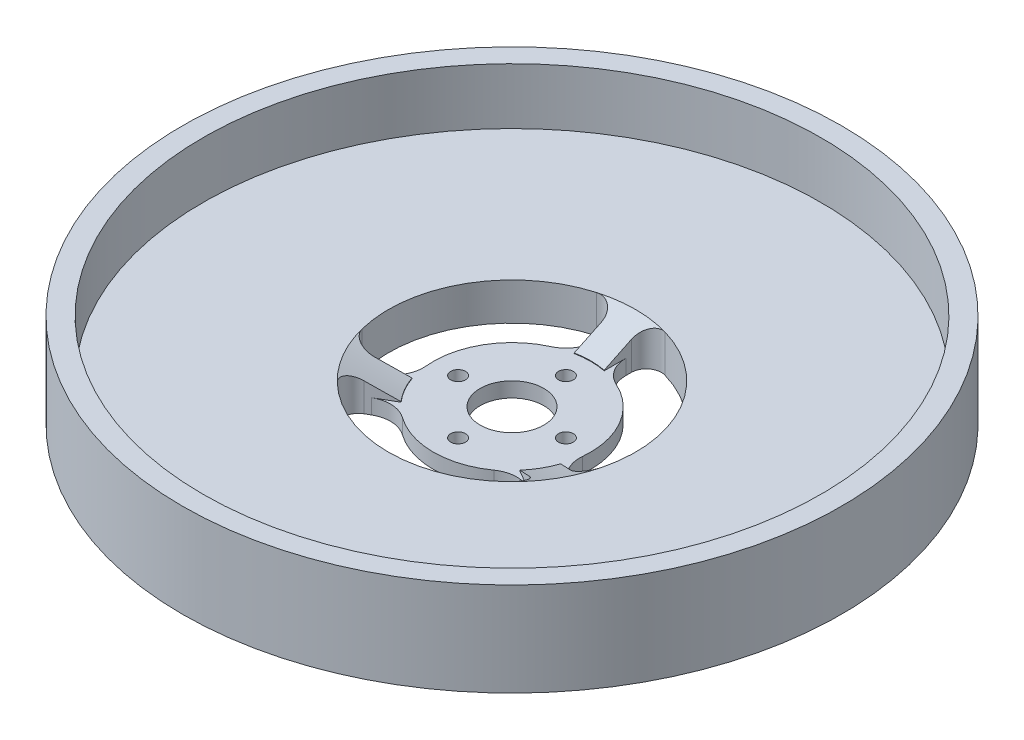
SolidWorks part; units mm, degrees
ref_plane "Front Plane" through (0, 0, 0) normal (0, 0, 1) x (1, 0, 0)
ref_plane "Top Plane" through (0, 0, 0) normal (0, 1, 0) x (1, 0, 0)
ref_plane "Right Plane" through (0, 0, 0) normal (1, 0, 0) x (0, 0, -1)
sketch "Sketch2" plane through (0, 0, 0) normal (0, 1, 0) x (1, 0, 0)
  circle A0 centre (0, 0) radius 44
extrude "Boss-Extrude2" add sketch "Sketch2" along normal blind 12.5
sketch "Sketch5" plane through (0, 12.5, 0) normal (0, 1, 0) x (1, 0, 0)
  circle A0 centre (0, 0) radius 41.25
  dimension "D1" = 82.5
extrude "Cut-Extrude2" cut sketch "Sketch5" against normal blind 7.5
sketch "Sketch6" plane through (0, 5, 0) normal (0, 1, 0) x (1, 0, 0)
  circle A0 centre (0, 0) radius 10.5
extrude "Cut-Extrude3" cut sketch "Sketch6" against normal blind 3
sketch "Sketch7" plane through (0, 2, 0) normal (0, 1, 0) x (1, 0, 0)
  circle A0 centre (0, 0) radius 4.25
  dimension "D1" = 8.5
extrude "Cut-Extrude4" cut sketch "Sketch7" against normal through all
sketch "Sketch8" plane through (0, 2, 0) normal (0, 1, 0) x (1, 0, 0)
  line L0 (-32.1696, 7.2) -> (36.5413, 7.2) construction
  circle A0 centre (0, 7.2) radius 0.99
  dimension "D1" = 7.2
extrude "Cut-Extrude5" cut sketch "Sketch8" against normal through all
pattern_circular "CirPattern2" count 4 over 360 about axis through (0, 2, 0) along (0, 1, 0) of "Cut-Extrude5"
sketch "Sketch11" plane through (0, 0, 0) normal (0, -1, 0) x (1, 0, 0)
  line L0 (0, 0) -> (0, -24.4942) construction
  line L1 (0, 0) -> (40.7412, 23.522) construction
  line L2 (-2, -10.3078) -> (-2, -16.3783)
  line L3 (0, 0) -> (-45.2396, 26.1191) construction
  line L4 (2, -10.3078) -> (2, -16.3783)
  line L5 (15.1841, 6.4571) -> (9.9268, 3.4218)
  line L6 (13.1841, 9.9212) -> (7.9268, 6.8859)
  line L7 (-7.9268, 6.8859) -> (-13.1841, 9.9212)
  line L8 (-15.1841, 6.4571) -> (-9.9268, 3.4218)
  circle A0 centre (0, 0) radius 10.5
  circle A1 centre (0, 0) radius 16.5
  dimension "D1" = 6
  dimension "D2" = 21
  dimension "D3" = 2
  dimension "D4" = 4
  dimension "D5" = 120
  dimension "D6" = 120
  dimension "D7" = 2
  dimension "D8" = 2
  dimension "D9" = 2
  dimension "D10" = 2
extrude "Cut-Extrude6" cut sketch "Sketch11" against normal blind 9 contours L6 A1 L7 A0 | L8 A1 L2 A0 | L4 A1 L5 A0 region at (-10.3663, 0, -5.985) region at (10.3663, 0, -5.985) region at (0, 0, 11.97)
chamfer "Chamfer1" distance 6 angle 26 3 edges at (-9.0933, 5, 5.25) (0, 5, -10.5) (9.0933, 5, 5.25) first distance on face at (0, 5, 41.25)
fillet "Fillet2" radius 4 6 edges at (7.9268, 1, 6.8859) (9.9268, 1, 3.4218) (2, 1, -10.3078) (-2, 1, -10.3078) (-9.9268, 1, 3.4218) (-7.9268, 1, 6.8859)
fillet "Fillet3" radius 2 6 edges at (15.1841, 2.5, 6.4571) (13.1841, 2.5, 9.9212) (-15.1841, 2.5, 6.4571) (-13.1841, 2.5, 9.9212) (2, 2.5, -16.3783) (-2, 2.5, -16.3783)
